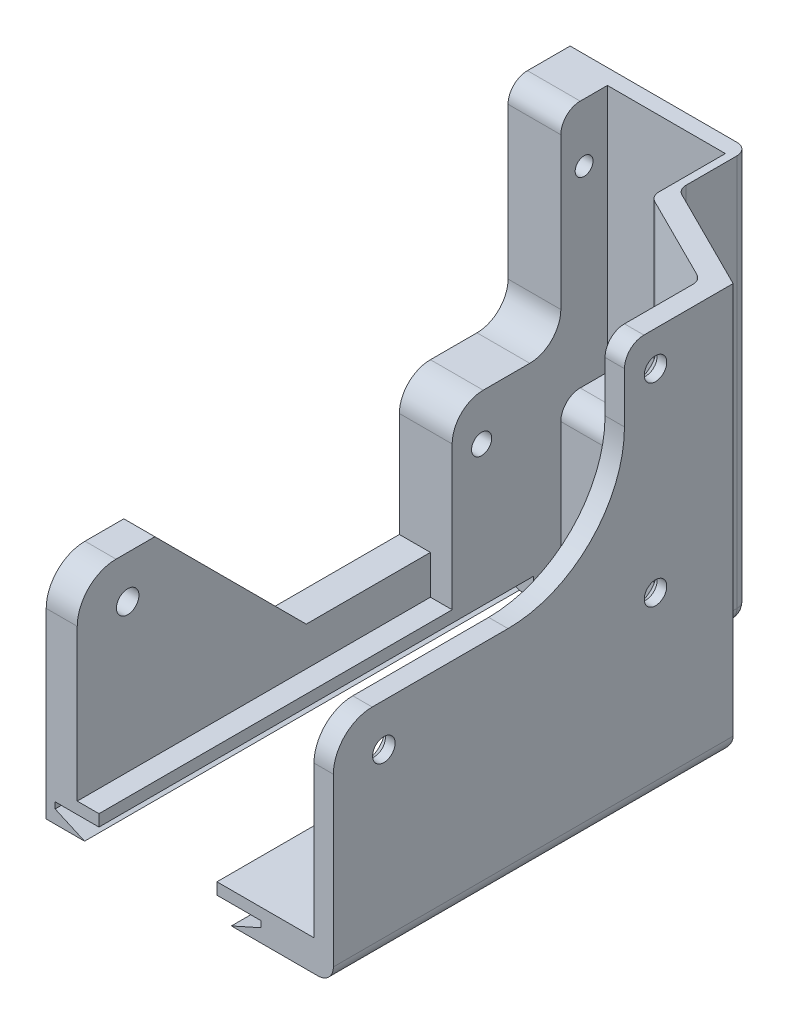
SolidWorks part; units mm, degrees
ref_plane "Спереди" through (0, 0, 0) normal (0, 0, 1) x (1, 0, 0)
ref_plane "Сверху" through (0, 0, 0) normal (0, 1, 0) x (1, 0, 0)
ref_plane "Справа" through (0, 0, 0) normal (1, 0, 0) x (0, 0, -1)
sketch "Эскиз1" plane through (0, 0, 0) normal (0, 1, 0) x (1, 0, 0)
  line L0 (0, 78.4998) -> (0, 0) construction
  line L1 (0, 0) -> (80.7208, 0) construction
sketch "Эскиз2" plane through (0, 0, 0) normal (0, 1, 0) x (1, 0, 0)
  line L0 (-16.9986, 152.8027) -> (29.0014, 152.8027)
  line L1 (29.0014, 152.8027) -> (29.0014, 134.8027)
  line L2 (29.0014, 134.8027) -> (57.0014, 120.8027)
  line L3 (57.0014, 120.8027) -> (57.0014, 17.8027)
  line L4 (57.0014, 17.8027) -> (27.0014, 17.8027)
  line L5 (27.0014, 17.8027) -> (27.0014, 148.8027)
  line L6 (27.0014, 148.8027) -> (-3.3986, 148.8027)
  line L7 (-3.3986, 148.8027) -> (-3.3986, 17.8027)
  line L8 (-3.3986, 17.8027) -> (-16.9986, 17.8027)
  line L9 (-16.9986, 17.8027) -> (-16.9986, 152.8027)
  dimension "D1" = 30.4
  dimension "D2" = 4
  dimension "D3" = 13.6
  dimension "D4" = 28
  dimension "D5" = 2
  dimension "D6" = 18
  dimension "D7" = 135
  dimension "D8" = 74
  dimension "D9" = 32
  dimension "D10" = 103
extrude "Бобышка-Вытянуть1" add sketch "Эскиз2" along normal blind 105
sketch "Эскиз3" plane through (0, 0, 0) normal (0, -1, 0) x (1, 0, 0)
  line L0 (27.0014, -148.8027) -> (27.0014, -17.8027) construction
  line L1 (-3.3986, -148.8027) -> (27.0014, -148.8027)
  line L2 (-3.3986, -148.8027) -> (-3.3986, -129.8027)
  line L3 (-3.3986, -129.8027) -> (27.0014, -129.8027)
  line L4 (27.0014, -148.8027) -> (27.0014, -129.8027)
  dimension "D1" = 19
extrude "Бобышка-Вытянуть2" add sketch "Эскиз3" against normal blind 3
sketch "Эскиз4" plane through (0, 3, 0) normal (0, 1, 0) x (1, 0, 0)
  line L0 (27.0014, 148.8027) -> (27.0014, 129.8027) construction
  line L1 (-3.3986, 148.8027) -> (27.0014, 148.8027)
  line L2 (-3.3986, 148.8027) -> (-3.3986, 136.8027)
  line L3 (-3.3986, 136.8027) -> (27.0014, 136.8027)
  line L4 (27.0014, 148.8027) -> (27.0014, 136.8027)
  dimension "D1" = 12
extrude "Бобышка-Вытянуть3" add sketch "Эскиз4" along normal blind 38
fillet "Скругление1" radius 5 1 edges at (11.8014, 41, -136.8027)
sketch "Эскиз5" plane through (0, 0, -17.8027) normal (0, 0, 1) x (1, 0, 0)
  line L0 (11.8014, 36) -> (11.8014, -10.7851) construction
  line L1 (27.0014, 36) -> (-3.3986, 36) construction
  line L2 (27.0014, -1.66) -> (27.0014, 5)
  line L3 (27.0014, 5) -> (38.3014, 5)
  line L4 (38.3014, 5) -> (38.3014, 3.4)
  line L5 (38.3014, 3.4) -> (27.0014, -1.66)
  line L6 (-14.6986, 5) -> (-14.6986, 3.4)
  line L7 (-3.3986, 5) -> (-14.6986, 5)
  line L8 (-3.3986, -1.66) -> (-3.3986, 5)
  line L9 (-14.6986, 3.4) -> (-3.3986, -1.66)
  line L10 (0, 0) -> (80.7208, 0) construction
  point P12 (-14.6986, 4.2)
  dimension "D1" = 53
  dimension "D2" = 1.6
  dimension "D3" = 6.66
  dimension "D4" = 5
  dimension "D5" = 11.3
  dimension "D6" = 15.2
extrude "Вырез-Вытянуть1" cut sketch "Эскиз5" against normal up to surface (112 mm away) up to face at (11.8014, 1.5, -129.8027)
sketch "Эскиз6" plane through (0, 105, 0) normal (0, 1, 0) x (1, 0, 0)
  line L0 (-16.9986, 17.8027) -> (52.0014, 17.8027)
  line L1 (27.0014, 17.8027) -> (57.0014, 17.8027) construction
  line L2 (52.0014, 17.8027) -> (52.0014, 117.3027)
  line L3 (52.0014, 117.3027) -> (27.0014, 129.8027)
  line L4 (27.0014, 129.8027) -> (27.0014, 108.8027)
  line L5 (27.0014, 148.8027) -> (27.0014, 17.8027) construction
  line L6 (27.0014, 108.8027) -> (-16.9986, 108.8027)
  line L7 (-16.9986, 152.8027) -> (-16.9986, 17.8027) construction
  line L8 (-16.9986, 108.8027) -> (-16.9986, 17.8027)
  line L9 (57.0014, 17.8027) -> (57.0014, 120.8027) construction
  line L10 (57.0014, 120.8027) -> (29.0014, 134.8027) construction
  line L11 (27.0014, 148.8027) -> (-3.3986, 148.8027) construction
  dimension "D1" = 5
  dimension "D2" = 40
extrude "Вырез-Вытянуть2" cut sketch "Эскиз6" against normal offset from surface (97 mm away) 3 up to face at (32.6514, 5, -73.8027)
sketch "Эскиз7" plane through (-16.9986, 0, 0) normal (-1, 0, 0) x (0, 0, 1)
  line L0 (-152.8027, 0) -> (-17.8027, 0) construction
  line L1 (-152.8027, 105) -> (-152.8027, 0) construction
  circle A0 centre (-116.4027, 41.2) radius 5
  dimension "D1" = 10
  dimension "D2" = 41.2
  dimension "D3" = 36.4
extrude "Вырез-Вытянуть3" cut sketch "Эскиз7" against normal blind 6.8
sketch "Эскиз8" plane through (-10.1986, 0, 0) normal (-1, 0, 0) x (0, 0, 1)
  circle A0 centre (-116.4027, 41.2) radius 2.6
  dimension "D1" = 5.2
extrude "Вырез-Вытянуть4" cut sketch "Эскиз8" against normal blind 20
chamfer "Фаска1" distance 3 angle 45 1 edges at (-10.1986, 41.2, -113.8027)
fillet "Скругление2" radius 3 4 edges at (52.0014, 56.5, -117.3027) (27.0014, 56.5, -129.8027) (29.0014, 52.5, -134.8027) (29.0014, 52.5, -152.8027)
sketch "Эскиз9" plane through (52.0014, 0, 0) normal (-1, 0, 0) x (0, 0, 1)
  line L0 (-100.8027, 125.7761) -> (-100.8027, 46) construction
  line L1 (-100.8027, 46) -> (-9.2893, 46) construction
  line L2 (-78.4998, 0) -> (0, 0) construction
  line L3 (-152.8027, 105) -> (-152.8027, 0) construction
  circle A0 centre (-100.8027, 46) radius 2.9
  circle A1 centre (-100.8027, 96) radius 2.9
  circle A2 centre (-30.8027, 46) radius 2.9
  dimension "D1" = 5.8
  dimension "D2" = 70
  dimension "D3" = 50
  dimension "D4" = 46
  dimension "D5" = 52
extrude "Вырез-Вытянуть5" cut sketch "Эскиз9" against normal through all
sketch "Эскиз10" plane through (52.0014, 0, 0) normal (-1, 0, 0) x (0, 0, 1)
  line L0 (-152.8027, 105) -> (-152.8027, 0) construction
  line L1 (-17.8027, 105) -> (-92.8027, 105)
  line L2 (-17.8027, 105) -> (-17.8027, 57)
  line L3 (-17.8027, 57) -> (-92.8027, 57)
  line L4 (-92.8027, 105) -> (-92.8027, 57)
  dimension "D1" = 48
  dimension "D2" = 60
extrude "Вырез-Вытянуть6" cut sketch "Эскиз10" against normal blind 20
fillet "Скругление3" radius 30 1 edges at (54.5014, 57, -92.8027)
sketch "Эскиз11" plane through (-16.9986, 0, 0) normal (-1, 0, 0) x (0, 0, 1)
  line L0 (-152.8027, 105) -> (-152.8027, 0) construction
  line L1 (-108.8027, 105) -> (-136.8027, 105)
  line L2 (-108.8027, 105) -> (-108.8027, 53)
  line L3 (-108.8027, 53) -> (-136.8027, 53)
  line L4 (-136.8027, 105) -> (-136.8027, 53)
  dimension "D1" = 16
  dimension "D2" = 52
extrude "Вырез-Вытянуть7" cut sketch "Эскиз11" against normal blind 20
fillet "Скругление4" radius 8 2 edges at (-10.1986, 53, -136.8027) (-10.1986, 53, -108.8027)
sketch "Эскиз12" plane through (0, 8, 0) normal (0, 1, 0) x (1, 0, 0)
  line L0 (26.0014, 152.8027) -> (-16.9986, 152.8027) construction
  line L1 (-16.9986, 17.8027) -> (-8.9986, 17.8027)
  line L2 (-16.9986, 17.8027) -> (-16.9986, 36.8027)
  line L3 (-16.9986, 36.8027) -> (-8.9986, 36.8027)
  line L4 (-8.9986, 17.8027) -> (-8.9986, 36.8027)
  dimension "D1" = 8
  dimension "D2" = 116
extrude "Бобышка-Вытянуть4" add sketch "Эскиз12" along normal up to surface (49 mm away) up to face at (54.5014, 57, -40.3027)
chamfer "Фаска2" distance 50 angle 45 1 edges at (-12.9986, 8, -36.8027)
fillet "Скругление5" radius 10 2 edges at (54.5014, 57, -17.8027) (-12.9986, 57, -17.8027)
sketch "Эскиз13" plane through (57.0014, 0, 0) normal (1, 0, 0) x (0, 0, -1)
  circle A0 centre (30.8027, 46) radius 2.9
extrude "Вырез-Вытянуть8" cut sketch "Эскиз13" against normal through all
chamfer "Фаска3" distance 2.5 angle 45 4 edges at (52.0014, 96, -97.9027) (52.0014, 46, -27.9027) (52.0014, 46, -97.9027) (-16.9986, 46, -33.7027)
sketch "Эскиз14" plane through (-16.9986, 0, 0) normal (-1, 0, 0) x (0, 0, 1)
  line L0 (-142.8027, 122.3898) -> (-142.8027, -15.2177) construction
  line L1 (-152.8027, 105) -> (-152.8027, 0) construction
  line L2 (-152.8027, 0) -> (-17.8027, 0) construction
  circle A0 centre (-142.8027, 90) radius 2.3
  circle A1 centre (-142.8027, 30) radius 2.3
  dimension "D2" = 4.6
  dimension "D3" = 60
  dimension "D4" = 30
  dimension "D1" = 10
extrude "Вырез-Вытянуть9" cut sketch "Эскиз14" against normal blind 15
fillet "Скругление6" radius 5 2 edges at (54.5014, 105, -92.8027) (-10.1986, 105, -136.8027)
fillet "Скругление7" radius 0.8 3 edges at (-16.9986, 41.2, -111.4027) (-16.9986, 30, -140.5027) (-16.9986, 90, -140.5027)
fillet "Скругление8" radius 4 6 edges at (43.8306, 0, -127.3881) (29.4495, 0, -135.0796) (4.5014, 0, -152.8027) (28.1228, 0, -151.924) (29.0014, 0, -143.2298) (57.0014, 0, -69.3027)
sketch "Эскиз15" plane through (0, 8, 0) normal (0, 1, 0) x (1, 0, 0)
  line L0 (-8.9986, 17.8027) -> (-8.9986, 86.8027) construction
  line L1 (-16.9986, 108.8027) -> (-8.9986, 108.8027)
  line L2 (-16.9986, 108.8027) -> (-16.9986, 68.3299)
  line L3 (-16.9986, 68.3299) -> (-8.9986, 68.3299)
  line L4 (-8.9986, 108.8027) -> (-8.9986, 68.3299)
extrude "Бобышка-Вытянуть5" add sketch "Эскиз15" along normal blind 10
